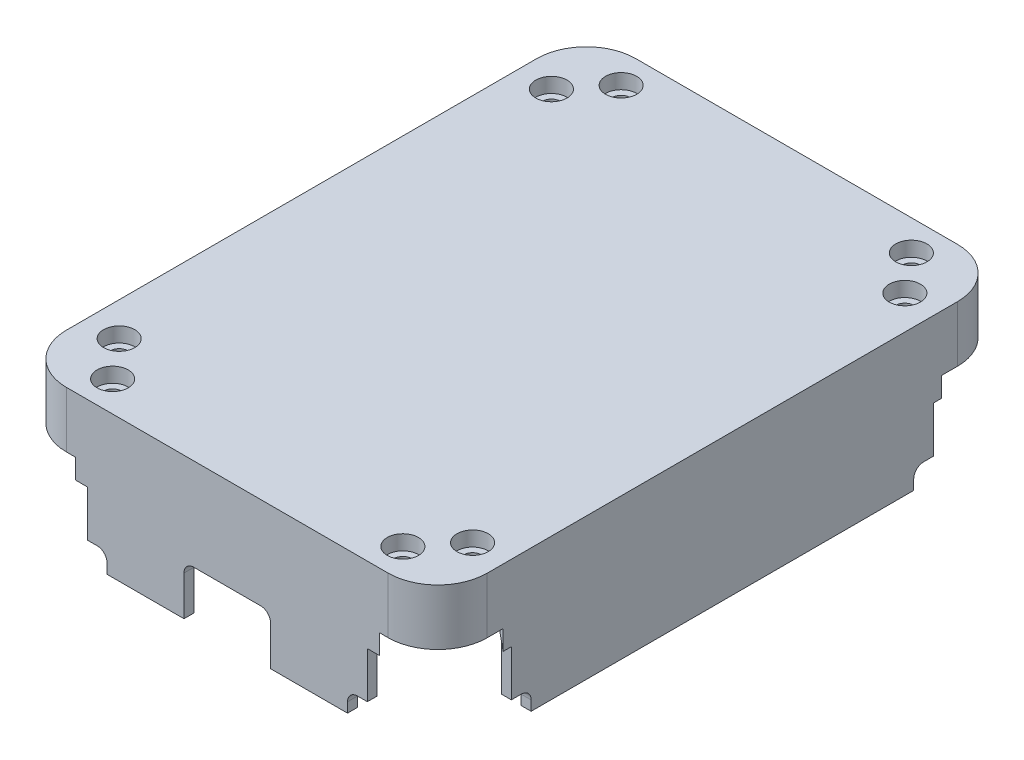
SolidWorks part; units mm, degrees
note: '?' marks a value the reader was unsure of.
material "3-D Printed ABS"
ref_plane "Front Plane" through (0, 0, 0) normal (0, 0, 1) x (1, 0, 0)
ref_plane "Top Plane" through (0, 0, 0) normal (0, 1, 0) x (1, 0, 0)
ref_plane "Right Plane" through (0, 0, 0) normal (1, 0, 0) x (0, 0, -1)
sketch "Sketch1" plane through (0, 0, 0) normal (0, 1, 0) x (1, 0, 0)
  line L1 (-53.975, -73.025) -> (53.975, -73.025)
  line L2 (-53.975, -73.025) -> (-53.975, 73.025)
  line L3 (-53.975, 73.025) -> (53.975, 73.025)
  line L4 (53.975, -73.025) -> (53.975, 73.025)
  line L5 (-53.975, -73.025) -> (53.975, 73.025) construction
  line L6 (-53.975, 73.025) -> (53.975, -73.025) construction
  point P0 (0, 0)
  dimension "D1" = 107.95
  dimension "D2" = 146.05
extrude "Boss-Extrude1" add sketch "Sketch1" against normal blind 2.54
sketch "Sketch13" plane through (0, 0, 0) normal (0, 1, 0) x (1, 0, 0)
  line L0 (0, 155.0212) -> (0, -155.0212) construction
  line L1 (0, 0) -> (-92.0171, 0) construction
  line L2 (53.975, -73.025) -> (53.975, 73.025) construction
  line L3 (53.975, -73.025) -> (28.575, -73.025)
  line L4 (53.975, -73.025) -> (53.975, -47.625)
  line L5 (53.975, -47.625) -> (28.575, -47.625)
  line L6 (28.575, -73.025) -> (28.575, -47.625)
  line L7 (-53.975, -73.025) -> (53.975, -73.025) construction
  line L8 (-28.575, -73.025) -> (-28.575, -47.625)
  line L9 (-53.975, -47.625) -> (-28.575, -47.625)
  line L10 (-53.975, -73.025) -> (-53.975, -47.625)
  line L11 (-53.975, -73.025) -> (-28.575, -73.025)
  line L12 (-53.975, 73.025) -> (-28.575, 73.025)
  line L13 (-53.975, 73.025) -> (-53.975, 47.625)
  line L14 (-53.975, 47.625) -> (-28.575, 47.625)
  line L15 (-28.575, 73.025) -> (-28.575, 47.625)
  line L16 (28.575, 73.025) -> (28.575, 47.625)
  line L17 (53.975, 47.625) -> (28.575, 47.625)
  line L18 (53.975, 73.025) -> (53.975, 47.625)
  line L19 (53.975, 73.025) -> (28.575, 73.025)
  dimension "D1" = 25.4
  dimension "D2" = 25.4
extrude "Boss-Extrude4" add sketch "Sketch13" against normal blind 19.431
sketch "Sketch2" plane through (0, 0, 0) normal (0, 1, 0) x (1, 0, 0)
  line L0 (0, 0) -> (100.1618, 0) construction
  line L1 (0, 0) -> (0, 86.3534) construction
  line L2 (53.975, 73.025) -> (-53.975, 73.025) construction
  line L3 (-53.975, 73.025) -> (-53.975, -73.025) construction
  line L4 (0, 0) -> (-53.975, 73.025) construction
  line L5 (0, 0) -> (-152.4, 0) construction
  line L6 (-152.4, 0) -> (-152.4, 152.4) construction
  line L7 (-152.4, 152.4) -> (0, 152.4) construction
  line L8 (0, 152.4) -> (0, 86.3534) construction
  line L9 (-152.4, 152.4) -> (0, 0) construction
  line L10 (-152.4, 152.4) -> (-41.275, 60.325) construction
  line L11 (-41.275, 60.325) -> (0, 26.1257) construction
  line L13 (-53.975, 44.9974) -> (-30.7521, 73.025) construction
  circle A0 centre (45.3264, 55.4354) radius 3.302
  circle A1 centre (37.2236, 65.2146) radius 3.302
  circle A2 centre (45.3264, -55.4354) radius 3.302
  circle A3 centre (37.2236, -65.2146) radius 3.302
  circle A4 centre (-37.2236, 65.2146) radius 3.302
  circle A5 centre (-45.3264, 55.4354) radius 3.302
  circle A6 centre (-45.3264, -55.4354) radius 3.302
  circle A7 centre (-37.2236, -65.2146) radius 3.302
  point P15 (-41.275, 60.325)
  dimension "D1" = 6.35
  dimension "D3" = 12.7
  dimension "D4" = 6.604
  dimension "D5" = 6.604
  dimension "D2" = 12.7
  dimension "D6" = 6.35
extrude "Cut-Extrude1" cut sketch "Sketch2" against normal through all
sketch "Sketch3" plane through (0, 0, 0) normal (0, 1, 0) x (1, 0, 0)
  line L0 (-53.975, 25.4) -> (53.975, 25.4) construction
  line L1 (-23.495, 60.325) -> (-19.05, 60.325)
  line L2 (-23.495, 60.325) -> (-23.495, 44.45)
  line L3 (-23.495, 44.45) -> (-19.05, 44.45)
  line L4 (-19.05, 60.325) -> (-19.05, 44.45)
  line L5 (19.05, 60.325) -> (19.05, 44.45)
  line L6 (23.495, 44.45) -> (19.05, 44.45)
  line L7 (23.495, 60.325) -> (23.495, 44.45)
  line L8 (23.495, 60.325) -> (19.05, 60.325)
  line L9 (-53.975, 73.025) -> (-53.975, -73.025) construction
  line L10 (53.975, -73.025) -> (53.975, 73.025) construction
  line L11 (0, 0) -> (0, 97.7255) construction
  line L12 (0, 50.8) -> (0, -46.9255) construction
  line L13 (23.495, -9.525) -> (19.05, -9.525)
  line L14 (23.495, -9.525) -> (23.495, 6.35)
  line L15 (23.495, 6.35) -> (19.05, 6.35)
  line L16 (19.05, -9.525) -> (19.05, 6.35)
  line L17 (-19.05, -9.525) -> (-19.05, 6.35)
  line L18 (-23.495, 6.35) -> (-19.05, 6.35)
  line L19 (-23.495, -9.525) -> (-23.495, 6.35)
  line L20 (-23.495, -9.525) -> (-19.05, -9.525)
  dimension "D1" = 15.875
  dimension "D2" = 4.445
  dimension "D3" = 19.05
  dimension "D4" = 25.4
  dimension "D5" = 44.45
extrude "Cut-Extrude2" [suppressed] cut sketch "Sketch3" against normal through all
fillet "Fillet1" radius 12.7 4 edges at (53.975, -9.7155, -73.025) (53.975, -9.7155, 73.025) (-53.975, -9.7155, 73.025) (-53.975, -9.7155, -73.025)
sketch "Sketch4" plane through (0, 0, 0) normal (0, 1, 0) x (1, 0, 0)
  line L0 (0, 0) -> (80.9727, -80.9727) construction
  line L1 (0, 0) -> (-80.9727, -80.9727) construction
  line L2 (69.1118, -51.1513) -> (28.7006, -10.7401)
  line L3 (28.7006, -10.7401) -> (10.7401, -28.7006)
  line L4 (10.7401, -28.7006) -> (51.1513, -69.1118)
  line L5 (51.1513, -69.1118) -> (69.1118, -51.1513)
  line L6 (0, 0) -> (0, -118.7381) construction
  line L7 (0, 0) -> (-98.4177, 0) construction
  line L8 (-51.1513, -69.1118) -> (-69.1118, -51.1513)
  line L9 (-69.1118, -51.1513) -> (-28.7006, -10.7401)
  line L10 (-28.7006, -10.7401) -> (-10.7401, -28.7006)
  line L11 (-10.7401, -28.7006) -> (-51.1513, -69.1118)
  line L12 (-69.1118, 51.1513) -> (-28.7006, 10.7401)
  line L13 (-51.1513, 69.1118) -> (-69.1118, 51.1513)
  line L14 (-10.7401, 28.7006) -> (-51.1513, 69.1118)
  line L15 (-28.7006, 10.7401) -> (-10.7401, 28.7006)
  line L16 (51.1513, 69.1118) -> (69.1118, 51.1513)
  line L17 (69.1118, 51.1513) -> (28.7006, 10.7401)
  line L18 (28.7006, 10.7401) -> (10.7401, 28.7006)
  line L19 (10.7401, 28.7006) -> (51.1513, 69.1118)
  point P6 (19.7204, -19.7204)
  dimension "D1" = 25.4
  dimension "D2" = 57.15
  dimension "D3" = 45
extrude "Cut-Extrude3" [suppressed] cut sketch "Sketch4" against normal blind 1.5875
sketch "Sketch6" [suppressed] plane through (0, 0, 0) normal (0, 1, 0) x (1, 0, 0)
  line L0 (46.3377, -44.1074) -> (34.6634, -32.4331) construction
  line L1 (0, 0) -> (0, -117.7376) construction
  line L2 (0, 0) -> (-151.7285, 0) construction
  line L4 (28.1601, -10.1996) -> (10.1996, -28.1601) construction
  line L5 (50.6107, -68.5712) -> (68.5712, -50.6107) construction
  text T0 "ESC" font "Century Gothic" height in points 22
  dimension "D1" = 45
  dimension "D2" = 20.32
  dimension "D3" = 20.32
extrude "Cut-Extrude5" [suppressed] cut sketch "Sketch6" against normal blind 3.175
sketch "Sketch5" plane through (0, 0, 0) normal (0, 1, 0) x (1, 0, 0)
  line L0 (41.275, 73.025) -> (-41.275, 73.025) construction
  line L1 (14.2875, 15.875) -> (-14.2875, 15.875)
  line L2 (14.2875, 15.875) -> (14.2875, 66.675)
  line L3 (14.2875, 66.675) -> (-14.2875, 66.675)
  line L4 (-14.2875, 15.875) -> (-14.2875, 66.675)
  point P4 (0, 15.875)
  dimension "D1" = 50.8
  dimension "D2" = 28.575
  dimension "D3" = 6.35
extrude "Cut-Extrude4" [suppressed] cut sketch "Sketch5" against normal blind 1.5875
ref_axis "Axis1" through (0, 0.3175, 0) along (0, -1, 0)?
pattern_circular "CirPattern1" [suppressed] count 4 over 360 about axis through (0, 0.3175, 0) along (0, -1, 0)
sketch "Sketch7" plane through (0, 0, 0) normal (0, 1, 0) x (1, 0, 0)
  line L0 (0, 0) -> (0, -54.962) construction
  line L1 (63.4018, -13.3522) -> (38.0018, -13.3522)
  line L2 (63.4018, -13.3522) -> (63.4018, 43.7978)
  line L3 (63.4018, 43.7978) -> (38.0018, 43.7978)
  line L4 (38.0018, -13.3522) -> (38.0018, 43.7978)
  line L5 (-38.0018, -13.3522) -> (-38.0018, 43.7978)
  line L6 (-63.4018, 43.7978) -> (-38.0018, 43.7978)
  line L7 (-63.4018, -13.3522) -> (-63.4018, 43.7978)
  line L8 (-63.4018, -13.3522) -> (-38.0018, -13.3522)
  line L9 (-41.275, -73.025) -> (41.275, -73.025) construction
  line L10 (38.5677, -40.64) -> (-18.5823, -40.64)
  line L11 (38.5677, -40.64) -> (38.5677, -66.04)
  line L12 (38.5677, -66.04) -> (-18.5823, -66.04)
  line L13 (-18.5823, -40.64) -> (-18.5823, -66.04)
  line L14 (38.5677, -40.64) -> (-18.5823, -66.04) construction
  line L15 (38.5677, -66.04) -> (-18.5823, -40.64) construction
  line L16 (19.844, -36.1003) -> (-37.306, -36.1003)
  line L17 (19.844, -36.1003) -> (19.844, -61.5003)
  line L18 (19.844, -61.5003) -> (-37.306, -61.5003)
  line L19 (-37.306, -36.1003) -> (-37.306, -61.5003)
  line L20 (19.844, -36.1003) -> (-37.306, -61.5003) construction
  line L21 (19.844, -61.5003) -> (-37.306, -36.1003) construction
  point P11 (9.9927, -53.34)
  point P18 (-8.731, -48.8003)
  dimension "D1" = 57.15
  dimension "D2" = 25.4
  dimension "D3" = 57.15
  dimension "D4" = 25.4
  dimension "D5" = 6.985
  dimension "D6" = 57.15
  dimension "D7" = 25.4
extrude "Cut-Extrude6" [suppressed] cut sketch "Sketch7" against normal blind 1.27
sketch "Sketch8" plane through (0, 0, 0) normal (0, 1, 0) x (1, 0, 0)
  line L7 (19.05, -31.75) -> (-19.05, -31.75)
  line L8 (19.05, -31.75) -> (19.05, 31.75)
  line L9 (19.05, 31.75) -> (-19.05, 31.75)
  line L10 (-19.05, -31.75) -> (-19.05, 31.75)
  point P0 (0, 0)
  dimension "D1" = 38.1
  dimension "D2" = 31.75
  dimension "D3" = 63.5
extrude "Boss-Extrude3" [suppressed] add sketch "Sketch8" along normal blind 2.54
sketch "Sketch11" plane through (0, 0, 0) normal (0, 1, 0) x (1, 0, 0)
  line L1 (19.05, -9.525) -> (-19.05, -9.525)
  line L2 (19.05, -9.525) -> (19.05, 6.35)
  line L3 (19.05, 6.35) -> (-19.05, 6.35)
  line L4 (-19.05, -9.525) -> (-19.05, 6.35)
extrude "Cut-Extrude9" [suppressed] cut sketch "Sketch11" against normal mid plane 2.54
sketch "Sketch12" [suppressed] plane through (0, 0, 0) normal (0, 1, 0) x (1, 0, 0)
  line L0 (-23.495, -9.525) -> (-19.05, -9.525) construction
  line L1 (12.7, -9.525) -> (-12.7, -9.525)
  line L2 (12.7, -9.525) -> (12.7, 6.35)
  line L3 (12.7, 6.35) -> (-12.7, 6.35)
  line L4 (-12.7, -9.525) -> (-12.7, 6.35)
  line L5 (-19.05, 6.35) -> (-23.495, 6.35) construction
  line L6 (19.05, 52.3875) -> (-19.05, 52.3875) construction
  line L7 (19.05, 60.325) -> (19.05, 44.45) construction
  line L8 (-19.05, 44.45) -> (-19.05, 60.325) construction
  line L9 (-12.7, 114.3) -> (-12.7, 98.425)
  line L10 (12.7, 98.425) -> (-12.7, 98.425)
  line L11 (12.7, 114.3) -> (12.7, 98.425)
  line L12 (12.7, 114.3) -> (-12.7, 114.3)
  point P8 (0, -9.525)
  dimension "D1" = 25.4
extrude "Cut-Extrude12" [suppressed] cut sketch "Sketch12" along normal through all
sketch "Sketch9" plane through (0, 0, 0) normal (0, 1, 0) x (1, 0, 0)
  line L1 (25.1579, -52.4084) -> (-25.6421, -52.4084)
  line L2 (25.1579, -52.4084) -> (25.1579, -1.6084)
  line L3 (25.1579, -1.6084) -> (-25.6421, -1.6084)
  line L4 (-25.6421, -52.4084) -> (-25.6421, -1.6084)
  line L5 (25.1579, -52.4084) -> (-25.6421, -1.6084) construction
  line L6 (25.1579, -1.6084) -> (-25.6421, -52.4084) construction
  point P0 (-0.2421, -27.0084)
  dimension "D1" = 50.8
  dimension "D2" = 50.8
fillet "Fillet2" [suppressed] radius 12.7
sketch "Sketch14" plane through (0, -19.431, 0) normal (0, -1, 0) x (1, 0, 0)
  line L0 (0, 0) -> (0, -152.4) construction
  line L1 (0, 0) -> (152.4, 0) construction
  line L2 (0, 0) -> (152.4, -152.4) construction
  line L3 (152.4, -152.4) -> (41.275, -60.325) construction
  line L4 (41.275, -60.325) -> (27.042, -48.5319) construction
  line L5 (27.042, -48.5319) -> (0, -26.1257) construction
  line L6 (20.692, -28.6742) -> (6.35, -45.9835)
  line L7 (6.35, -45.9835) -> (139.0382, -155.9252)
  line L8 (139.0382, -155.9252) -> (153.3802, -138.6158)
  line L9 (153.3802, -138.6158) -> (20.692, -28.6742)
  line L10 (-20.692, -28.6742) -> (-6.35, -45.9835)
  line L11 (-153.3802, -138.6158) -> (-20.692, -28.6742)
  line L12 (-6.35, -45.9835) -> (-139.0382, -155.9252)
  line L13 (-139.0382, -155.9252) -> (-153.3802, -138.6158)
  line L14 (-153.3802, 138.6158) -> (-20.692, 28.6742)
  line L15 (-139.0382, 155.9252) -> (-153.3802, 138.6158)
  line L16 (-6.35, 45.9835) -> (-139.0382, 155.9252)
  line L17 (-20.692, 28.6742) -> (-6.35, 45.9835)
  line L18 (20.692, 28.6742) -> (6.35, 45.9835)
  line L19 (139.0382, 155.9252) -> (153.3802, 138.6158)
  line L20 (153.3802, 138.6158) -> (20.692, 28.6742)
  line L21 (6.35, 45.9835) -> (139.0382, 155.9252)
  line L22 (41.275, -73.025) -> (-41.275, -73.025) construction
  line L23 (53.975, 60.325) -> (53.975, -60.325) construction
  point P3 (13.521, -37.3288)
  point P6 (41.275, -60.325)
  dimension "D1" = 152.4
  dimension "D2" = 152.4
  dimension "D3" = 6.35
  dimension "D4" = 11.2395
  dimension "D5" = 12.7
  dimension "D6" = 12.7
extrude "Cut-Extrude13" cut sketch "Sketch14" against normal blind 5.08
sketch "Sketch15" plane through (0, 0, 0) normal (0, 1, 0) x (1, 0, 0)
  line L0 (0, 0) -> (72.5178, 0) construction
  line L1 (0, 0) -> (0, 124.598) construction
  circle A0 centre (-45.3264, 55.4354) radius 5.08
  circle A1 centre (45.3264, 55.4354) radius 5.08
  circle A2 centre (37.2236, 65.2146) radius 5.08
  circle A3 centre (45.3264, -55.4354) radius 5.08
  circle A4 centre (37.2236, -65.2146) radius 5.08
  circle A5 centre (-37.2236, -65.2146) radius 5.08
  circle A6 centre (-37.2236, 65.2146) radius 5.08
  circle A7 centre (-45.3264, -55.4354) radius 5.08
extrude "Boss-Extrude5" add sketch "Sketch15" against normal offset from surface (11.811 mm away) 2.54 up to face at (-41.6508, -14.351, -60.7008)
hole_wizard "M4 Clearance Hole1" [suppressed] positions "Sketch18" profile "Sketch16" hole size "M4" standard "ANSI Metric"
sketch "Sketch18" plane through (0, -19.05, 0) normal (0, -1, 0) x (-1, 0, 0)
  point P0 (41.275, 60.325)
  point P3 (41.275, -60.325)
  point P6 (-41.275, -60.325)
  point P9 (-41.275, 60.325)
sketch "Sketch16" plane through (-41.275, -19.05, -60.325) normal (1, 0, 0) x (0, 0, -1)
  line L0 (0, 0) -> (0, 19.05)
  line L1 (0, 19.05) -> (2.25, 19.05)
  line L2 (2.25, 19.05) -> (2.25, 0)
  line L5 (2.25, 0) -> (0, 0)
  line L11 (0, -6.35) -> (0, 107.95) construction
  dimension "Thru Hole Dia." = 4.5
  dimension "Thru Hole Depth" = 19.05
hole_wizard "CBORE for M4 SHCS1" [suppressed] positions "Sketch21" profile "Sketch20" counterbore size "M4" standard "ANSI Metric"
sketch "Sketch21" [suppressed] plane through (0, 0, 0) normal (0, 1, 0) x (1, 0, 0)
  point P0 (41.275, 60.325)
  point P3 (-41.275, 60.325)
  point P6 (-41.275, -60.325)
  point P9 (41.275, -60.325)
sketch "Sketch20" plane through (41.275, 0, -60.325) normal (1, 0, 0) x (0, 0, 1)
  line L0 (0, 0) -> (0, 24.13)
  line L1 (0, 24.13) -> (2.25, 24.13)
  line L3 (2.25, 24.13) -> (2.25, 4)
  line L4 (2.25, 4) -> (4, 4)
  line L5 (4, 4) -> (4, 0)
  line L7 (4, 0) -> (0, 0)
  line L11 (0, -6.35) -> (0, 107.95) construction
  dimension "Thru Hole Dia." = 4.5
  dimension "Thru Hole Depth" = 24.13
  dimension "C'Bore Dia." = 8
  dimension "C'Bore Depth" = 4
sketch "Sketch23" plane through (0, -14.351, 0) normal (0, -1, 0) x (1, 0, 0)
  circle A0 centre (-45.3264, -55.4354) radius 2.25
  circle A1 centre (-37.2236, -65.2146) radius 2.25
  dimension "D1" = 4.5
  dimension "D2" = 4.5
extrude "Cut-Extrude14" cut sketch "Sketch23" against normal through all
sketch "Sketch24" plane through (0, 0, 0) normal (0, 1, 0) x (1, 0, 0)
  circle A0 centre (-45.3264, 55.4354) radius 4
  circle A1 centre (-37.2236, 65.2146) radius 4
  dimension "D1" = 8
  dimension "D2" = 8
extrude "Cut-Extrude15" cut sketch "Sketch24" against normal blind 3.81
mirror "Mirror1" about plane through (0, 0, 0) normal (0, 0, 1) of "Cut-Extrude15", "Cut-Extrude14"
mirror "Mirror2" about plane through (0, 0, 0) normal (1, 0, 0) of "Cut-Extrude15", "Cut-Extrude14", "Mirror1"
fillet "Fillet3" radius 12.7 4 edges at (-28.575, -8.4455, -47.625) (28.575, -8.4455, -47.625) (28.575, -8.4455, 47.625) (-28.575, -8.4455, 47.625)
sketch "Sketch25" plane through (0, 0, 0) normal (0, 1, 0) x (1, 0, 0)
  line L0 (0, 0) -> (0, -33.9706) construction
  line L1 (0, 0) -> (63.8751, 0) construction
  circle A0 centre (30.0609, 0) radius 3.4925
  circle A1 centre (30.0609, -24.9682) radius 3.4925
  circle A2 centre (30.0609, 24.9682) radius 3.4925
  circle A3 centre (-30.0609, 24.9682) radius 3.4925
  circle A4 centre (-30.0609, -24.9682) radius 3.4925
  circle A5 centre (-30.0609, 0) radius 3.4925
  dimension "D1" = 6.985
  dimension "D2" = 6.985
  dimension "D3" = 24.9682
  dimension "D4" = 30.0609
extrude "GimbalMount1" [suppressed] cut sketch "Sketch25" against normal through all
sketch "Sketch26" [suppressed] plane through (0, 0, 0) normal (0, 1, 0) x (1, 0, 0)
  circle A0 centre (30.0609, -24.9682) radius 5.715
  circle A1 centre (30.0609, 0) radius 5.715
  circle A2 centre (30.0609, 24.9682) radius 5.715
  circle A3 centre (-30.0609, -24.9682) radius 5.715
  circle A4 centre (-30.0609, 0) radius 5.715
  circle A5 centre (-30.0609, 24.9682) radius 5.715
  dimension "D1" = 11.43
extrude "GimbalMount2" [suppressed] cut sketch "Sketch26" against normal blind 1.524
fillet "Fillet4" radius 1.016 8 edges at (-45.3264, -14.351, 52.1334) (-37.2236, -14.351, 61.9126) (37.2236, -14.351, 68.5166) (45.3264, -14.351, 58.7374) (-45.3264, -14.351, -52.1334) (-37.2236, -14.351, -61.9126) (37.2236, -14.351, -68.5166) (45.3264, -14.351, -58.7374)
sketch "Sketch27" plane through (0, -2.54, 0) normal (0, -1, 0) x (1, 0, 0)
  line L1 (35.9208, -73.025) -> (-35.9208, -73.025)
  line L2 (35.9208, -73.025) -> (35.9208, -70.485)
  line L3 (35.9208, -70.485) -> (-35.9208, -70.485)
  line L4 (-35.9208, -73.025) -> (-35.9208, -70.485)
  line L6 (0, 0) -> (0, -45.0707) construction
  line L7 (0, 0) -> (-77.1364, 0) construction
  line L8 (-35.9208, 73.025) -> (-35.9208, 70.485)
  line L9 (35.9208, 70.485) -> (-35.9208, 70.485)
  line L10 (35.9208, 73.025) -> (35.9208, 70.485)
  line L11 (35.9208, 73.025) -> (-35.9208, 73.025)
  line L13 (53.975, -54.1469) -> (51.435, -54.1469)
  line L14 (53.975, -54.1469) -> (53.975, 54.1469)
  line L15 (53.975, 54.1469) -> (51.435, 54.1469)
  line L16 (51.435, -54.1469) -> (51.435, 54.1469)
  line L17 (-51.435, -54.1469) -> (-51.435, 54.1469)
  line L18 (-53.975, 54.1469) -> (-51.435, 54.1469)
  line L19 (-53.975, -54.1469) -> (-53.975, 54.1469)
  line L20 (-53.975, -54.1469) -> (-51.435, -54.1469)
  line L22 (28.575, -64.3985) -> (38.9863, -73.025) construction
  line L23 (-38.9863, -73.025) -> (-28.575, -64.3985) construction
  line L24 (28.575, -73.025) -> (-28.575, -73.025) construction
  line L25 (53.975, -56.2515) -> (43.5637, -47.625) construction
  line L26 (53.975, 47.625) -> (53.975, -47.625) construction
  line L27 (43.5637, 47.625) -> (53.975, 56.2515) construction
  dimension "D1" = 2.54
  dimension "D2" = 2.54
extrude "Boss-Extrude6" add sketch "Sketch27" along normal blind 33.782
sketch "Sketch28" plane through (0, 0, -73.025) normal (0, 0, -1) x (-1, 0, 0)
  line L0 (-41.275, 0) -> (41.275, 0) construction
  line L1 (-17.526, -36.322) -> (17.526, -36.322)
  line L2 (-16.891, -28.702) -> (-16.891, -21.3995)
  line L3 (-14.351, -18.8595) -> (14.351, -18.8595)
  line L4 (16.891, -28.702) -> (16.891, -21.3995)
  line L5 (35.9208, -36.322) -> (-35.9208, -36.322) construction
  line L6 (19.431, -31.242) -> (27.051, -31.242)
  line L7 (0, -18.8595) -> (0, 0) construction
  line L8 (17.526, -36.322) -> (29.591, -36.322)
  line L9 (29.591, -33.782) -> (29.591, -36.322)
  line L11 (-19.431, -31.242) -> (-27.051, -31.242)
  line L13 (-17.526, -36.322) -> (-29.591, -36.322)
  line L14 (-29.591, -33.782) -> (-29.591, -36.322)
  arc A0 (-29.591, -33.782) -> (-27.051, -31.242) centre (-27.051, -33.782) cw
  arc A1 (-19.431, -31.242) -> (-16.891, -28.702) centre (-19.431, -28.702) ccw
  arc A2 (-16.891, -21.3995) -> (-14.351, -18.8595) centre (-14.351, -21.3995) cw
  arc A3 (14.351, -18.8595) -> (16.891, -21.3995) centre (14.351, -21.3995) cw
  arc A4 (16.891, -28.702) -> (19.431, -31.242) centre (19.431, -28.702) ccw
  arc A5 (27.051, -31.242) -> (29.591, -33.782) centre (27.051, -33.782) cw
  point P5 (0, -36.322)
  point P19 (-29.591, -31.242)
  point P25 (-16.891, -18.8595)
  point P28 (16.891, -18.8595)
  point P34 (29.591, -31.242)
  dimension "D7" = 2.54
  dimension "D1" = 17.4625
  dimension "D2" = 33.782
  dimension "D3" = 10.16
  dimension "D4" = 5.08
  dimension "D5" = 10.16
  dimension "D6" = 5.08
extrude "Cut-Extrude16" cut sketch "Sketch28" against normal blind 41.656
sketch "Sketch29" plane through (-53.975, 0, 0) normal (-1, 0, 0) x (0, 0, 1)
  line L0 (0, -36.322) -> (0, -17.4257) construction
  line L1 (-54.1469, -36.322) -> (-49.0669, -36.322)
  line L2 (-54.1469, -36.322) -> (-54.1469, -31.242)
  line L3 (-54.1469, -31.242) -> (-51.6069, -31.242)
  line L4 (-49.0669, -36.322) -> (-49.0669, -33.782)
  line L5 (54.1469, -36.322) -> (-54.1469, -36.322) construction
  line L6 (49.0669, -36.322) -> (49.0669, -33.782)
  line L7 (54.1469, -31.242) -> (51.6069, -31.242)
  line L8 (54.1469, -36.322) -> (54.1469, -31.242)
  line L9 (54.1469, -36.322) -> (49.0669, -36.322)
  arc A0 (-49.0669, -33.782) -> (-51.6069, -31.242) centre (-51.6069, -33.782) ccw
  arc A1 (49.0669, -33.782) -> (51.6069, -31.242) centre (51.6069, -33.782) cw
  dimension "D1" = 2.54
  dimension "D2" = 5.08
  dimension "D3" = 5.08
extrude "Cut-Extrude17" cut sketch "Sketch29" against normal through all
sketch "Sketch30" plane through (0, 0, 73.025) normal (0, 0, 1) x (1, 0, 0)
  line L0 (0, -36.322) -> (0, -22.969) construction
  line L1 (-35.9208, -36.322) -> (-30.8408, -36.322)
  line L2 (-35.9208, -36.322) -> (-35.9208, -31.242)
  line L3 (-35.9208, -31.242) -> (-33.3808, -31.242)
  line L4 (-30.8408, -36.322) -> (-30.8408, -33.782)
  line L5 (35.9208, -36.322) -> (-35.9208, -36.322) construction
  line L6 (30.8408, -36.322) -> (30.8408, -33.782)
  line L7 (35.9208, -31.242) -> (33.3808, -31.242)
  line L8 (35.9208, -36.322) -> (35.9208, -31.242)
  line L9 (35.9208, -36.322) -> (30.8408, -36.322)
  arc A0 (-30.8408, -33.782) -> (-33.3808, -31.242) centre (-33.3808, -33.782) ccw
  arc A1 (30.8408, -33.782) -> (33.3808, -31.242) centre (33.3808, -33.782) cw
  dimension "D1" = 2.54
  dimension "D2" = 5.08
  dimension "D3" = 5.08
extrude "Cut-Extrude18" cut sketch "Sketch30" against normal through all
sketch "Sketch31" plane through (0, 0, 73.025) normal (0, 0, 1) x (1, 0, 0)
  line L0 (30.8408, -36.322) -> (-30.8408, -36.322) construction
  line L1 (-11.1125, -36.322) -> (11.1125, -36.322)
  line L2 (-11.1125, -36.322) -> (-11.1125, -23.622)
  line L3 (-11.1125, -23.622) -> (11.1125, -23.622)
  line L4 (11.1125, -36.322) -> (11.1125, -23.622)
  line L5 (0, -23.622) -> (0, -15.4197) construction
  line L6 (-41.275, 0) -> (41.275, 0) construction
  point P10 (0, 0)
  dimension "D1" = 12.7
  dimension "D2" = 22.225
extrude "Cut-Extrude19" cut sketch "Sketch31" against normal up to next
fillet "Fillet5" radius 2.54 2 edges at (11.1125, -23.622, 71.755) (-11.1125, -23.622, 71.755)
equation "\"Plate Thickness\"= \"Plate Thickness@Quad Assemb.sldasm\""
equation "\"D1@Boss-Extrude1\"=\"Plate Thickness\""
equation "\"Plate Dim X\"= \"Plate Dim X@Quad Assemb.sldasm\""
equation "\"Plate Dim Y\"= \"Plate Dim Y@Quad Assemb.sldasm\""
equation "\"D1@Boss-Extrude4\"=\"Component Y@Quad Assemb.sldasm\"-\"ArmBase@Arm V3_2-1.Part\""
equation "\"D4@Sketch14\"=\"ArmBase@Arm V3_2-1.Part\"/2+.005"
equation "\"Dowell Width\"= \"Dowell Width@Quad Assemb.sldasm\""
equation "\"D1@Sketch2\"=\"Dowell Width\""
equation "\"Dowell Height\"= \"Dowell Height@Quad Assemb.sldasm\""
equation "\"D1@Boss-Extrude5\"=\"Dowell Height\""
equation "\"GimbalMount1\"= if ( \"Gimbal Mount@Quad Assemb.sldasm\" = 1 , \"unsuppressed\" , \"suppressed\" )"
equation "\"GimbalMount2\"= if ( \"Gimbal Mount@Quad Assemb.sldasm\" = 1 , \"unsuppressed\" , \"suppressed\" )"
equation "\"D1@Boss-Extrude6\"=\"Component Y@Quad Assemb.sldasm\"-.31"
equation "\"D1@Sketch28\"=\"radio rx Z@Quad Assemb.sldasm\"+3/16"
equation "\"D2@Sketch28\"=\"radio rx x@quad assemb.sldasm\"+.2"
equation "\"D4@Sketch2\"=\"Dowell Width\"+0.01in"
equation "\"D5@Sketch2\"=\"Dowell Width\"+0.01in"
equation "\"D6@Sketch2\"=\"Dowell Width\""
